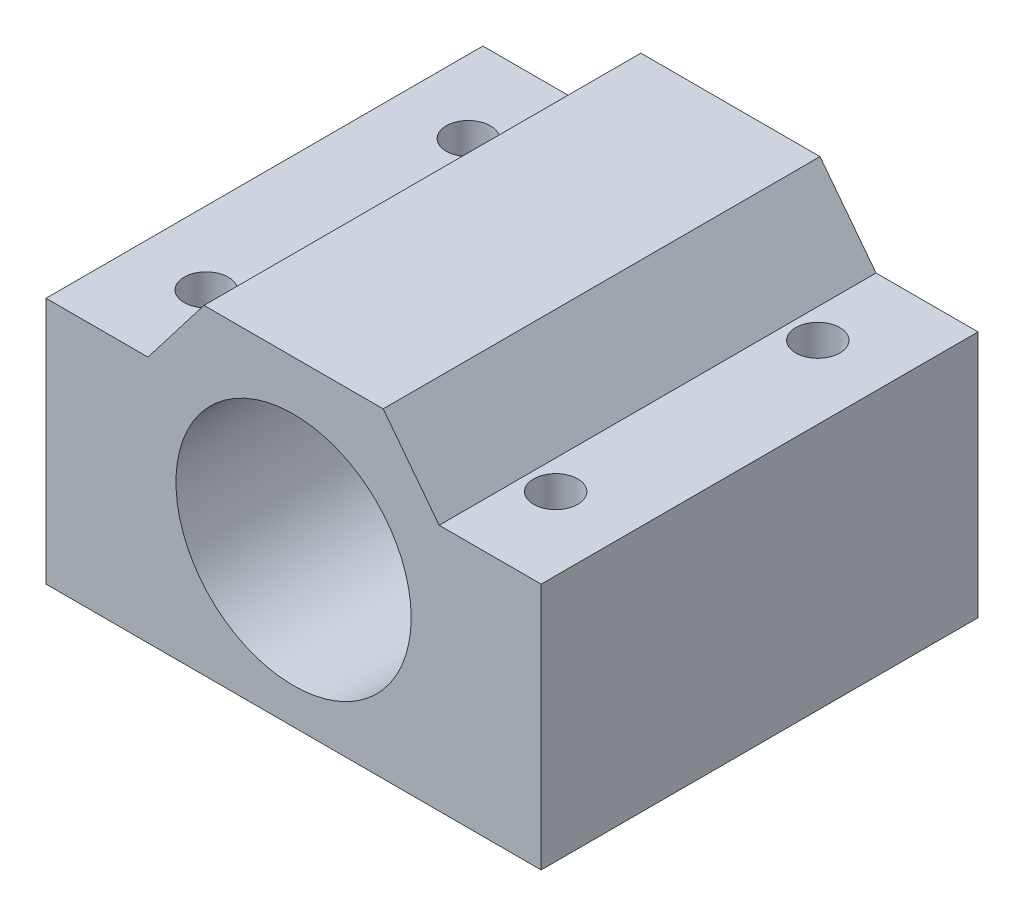
SolidWorks part; units mm, degrees
ref_plane "前视基准面" through (0, 0, 0) normal (0, 0, 1) x (1, 0, 0)
ref_plane "上视基准面" through (0, 0, 0) normal (0, 1, 0) x (1, 0, 0)
ref_plane "右视基准面" through (0, 0, 0) normal (1, 0, 0) x (0, 0, -1)
sketch "草图1" plane through (0, 0, 0) normal (0, 1, 0) x (1, 0, 0)
  line L0 (1.2257, 17.9561) -> (1.2257, -12.0439) construction
  line L1 (-15.7743, 17.9561) -> (18.2257, 17.9561)
  line L2 (-15.7743, 17.9561) -> (-15.7743, -12.0439)
  line L3 (-15.7743, -12.0439) -> (18.2257, -12.0439)
  line L4 (18.2257, 17.9561) -> (18.2257, -12.0439)
  line L5 (-15.7743, 2.9561) -> (18.2257, 2.9561) construction
  circle A0 centre (-10.7743, 11.9561) radius 1.5157
  circle A1 centre (13.2257, 11.9561) radius 1.5157
  circle A2 centre (13.2257, -6.0439) radius 1.5157
  circle A3 centre (-10.7743, -6.0439) radius 1.5157
  dimension "D3" = 24
  dimension "D1" = 34
  dimension "D2" = 30
  dimension "D4" = 18
extrude "凸台-拉伸1" add sketch "草图1" along normal blind 17
sketch "草图3" plane through (0, 0, 12.0439) normal (0, 0, 1) x (1, 0, 0)
  line L0 (1.2257, 17) -> (1.2257, -49983) construction
  line L1 (-15.7743, 17) -> (18.2257, 17) construction
  line L2 (-15.7743, 0) -> (18.2257, 0) construction
  line L3 (-8.7743, 17) -> (-4.9264, 22)
  line L4 (-4.9264, 22) -> (7.3778, 22)
  line L5 (11.2257, 17) -> (7.3778, 22)
  line L6 (-8.7743, 17) -> (11.2257, 17)
  line L7 (11.2257, 17) -> (11.2173, 16.9552)
  point P4 (1.2257, 17)
  point P7 (1.2257, 0)
  point P13 (1.2257, 22)
  line M7 (18.2257, 17) -> (-15.7743, 17)
  dimension "D1" = 5
  dimension "D2" = 20
extrude "凸台-拉伸3" add sketch "草图3" against normal up to surface (30 mm away) contours L0 L4 L3 L6 | L4 L0 L5 M7 region at (1.2257, 19.3015, 12.0439) up to face at (1.2257, 8.5, -17.9561)
sketch "草图4" plane through (0, 0, 12.0439) normal (0, 0, 1) x (1, 0, 0)
  line L0 (1.2257, 22) -> (1.2257, 0) construction
  line L1 (-4.9264, 22) -> (7.3778, 22) construction
  line L2 (-15.7743, 0) -> (18.2257, 0) construction
  circle A0 centre (1.2257, 10.5347) radius 8.0755
extrude "切除-拉伸1" cut sketch "草图4" against normal up to surface (30 mm away) up to face at (1.2257, 14, -17.9561)
